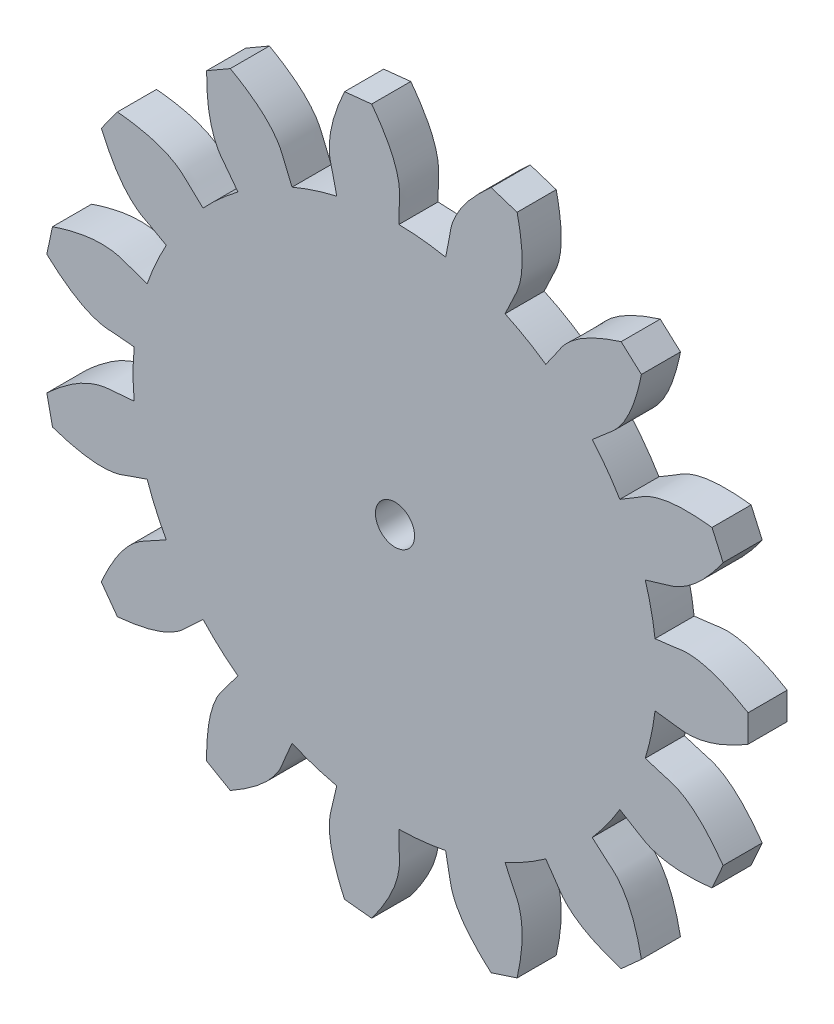
SolidWorks part; units mm, degrees
ref_plane "Front Plane" through (0, 0, 0) normal (0, 0, 1) x (1, 0, 0)
ref_plane "Top Plane" through (0, 0, 0) normal (0, 1, 0) x (1, 0, 0)
ref_plane "Right Plane" through (0, 0, 0) normal (1, 0, 0) x (0, 0, -1)
sketch "Sketch1" plane through (0, 0, 0) normal (0, 0, 1) x (1, 0, 0)
  line L0 (-8.1955, 56.7867) -> (-3.7902, 57.2497)
  line L2 (15.6103, 55.2106) -> (19.823, 53.8418)
  line L3 (36.7169, 44.0881) -> (40.0087, 41.1242)
  line L4 (51.4748, 25.3424) -> (53.2764, 21.2959)
  line L5 (57.3323, 2.2148) -> (57.3323, -2.2148)
  line L6 (53.2764, -21.2959) -> (51.4748, -25.3424)
  line L7 (40.0087, -41.1242) -> (36.7169, -44.0881)
  line L8 (19.823, -53.8418) -> (15.6103, -55.2106)
  line L9 (-3.7902, -57.2497) -> (-8.1955, -56.7867)
  line L10 (-26.7481, -50.7586) -> (-30.5842, -48.5438)
  line L11 (-45.081, -35.4908) -> (-47.6846, -31.9073)
  line L12 (-55.6189, -14.0864) -> (-56.5399, -9.7537)
  line L13 (-56.5399, 9.7537) -> (-55.6189, 14.0864)
  line L14 (-47.6846, 31.9073) -> (-45.081, 35.4908)
  line L15 (-30.5842, 48.5438) -> (-26.7481, 50.7586)
  arc A0 (-9.4604, 41.4593) -> (-16.7156, 39.102) centre (0, 0) ccw
  arc A1 (-25.5055, 34.0271) -> (-31.1746, 28.9226) centre (0, 0) ccw
  arc A2 (-37.1405, 20.7113) -> (-40.2433, 13.7423) centre (0, 0) ccw
  arc A3 (-42.3536, 3.8143) -> (-42.3536, -3.8143) centre (0, 0) ccw
  arc A4 (-40.2433, -13.7423) -> (-37.1405, -20.7113) centre (0, 0) ccw
  arc A5 (8.2205, 41.7229) -> (0.6338, 42.5203) centre (0, 0) ccw
  arc A6 (24.48, 34.7722) -> (17.8735, 38.5864) centre (0, 0) ccw
  arc A7 (36.5067, 21.809) -> (32.0228, 27.9806) centre (0, 0) ccw
  arc A8 (42.2211, 5.0749) -> (40.635, 12.5367) centre (0, 0) ccw
  arc A9 (40.635, -12.5367) -> (42.2211, -5.0749) centre (0, 0) ccw
  arc A10 (32.0228, -27.9806) -> (36.5067, -21.809) centre (0, 0) ccw
  arc A11 (17.8735, -38.5864) -> (24.48, -34.7722) centre (0, 0) ccw
  arc A12 (0.6338, -42.5203) -> (8.2205, -41.7229) centre (0, 0) ccw
  arc A13 (-16.7156, -39.102) -> (-9.4604, -41.4593) centre (0, 0) ccw
  arc A14 (-31.1746, -28.9226) -> (-25.5055, -34.0271) centre (0, 0) ccw
  spline S0 degree 3 poles (0.6338, 42.5203) (0.6362, 43.2787) (0.6708, 44.2001) (0.6715, 45.8052) (0.7748, 46.9365) (0.3722, 51.1441) (-1.8992, 54.7005) (-3.7902, 57.2497) knots 0 0 0 0 0.143931 0.175966 0.304305 0.357154 1 1 1 1
  spline S1 degree 3 poles (-9.4604, 41.4593) (-9.6204, 42.2007) (-9.8459, 43.0948) (-10.1802, 44.6647) (-10.5165, 45.7497) (-10.9975, 49.9491) (-9.5152, 53.9) (-8.1955, 56.7867) knots 0 0 0 0 0.143931 0.175966 0.304305 0.357154 1 1 1 1
  spline S2 degree 3 poles (17.8735, 38.5864) (18.1842, 39.2783) (18.5906, 40.106) (19.2441, 41.5721) (19.7986, 42.5635) (21.1422, 46.5711) (20.5137, 50.7438) (19.823, 53.8418) knots 0 0 0 0 0.143931 0.175966 0.304305 0.357154 1 1 1 1
  spline S3 degree 3 poles (8.2205, 41.7229) (8.3759, 42.4653) (8.5336, 43.3737) (8.8666, 44.9439) (9.0008, 46.0719) (10.2694, 50.1039) (13.2305, 53.1103) (15.6103, 55.2106) knots 0 0 0 0 0.143931 0.175966 0.304305 0.357154 1 1 1 1
  spline S4 degree 3 poles (32.0228, 27.9806) (32.5881, 28.4863) (33.296, 29.0772) (34.4892, 30.1507) (35.399, 30.8309) (38.2565, 33.9455) (39.3796, 38.0131) (40.0087, 41.1242) knots 0 0 0 0 0.143931 0.175966 0.304305 0.357154 1 1 1 1
  spline S5 degree 3 poles (24.48, 34.7722) (24.9239, 35.3872) (25.4375, 36.1529) (26.3804, 37.4519) (26.9618, 38.4278) (29.7607, 41.5952) (33.6886, 43.1373) (36.7169, 44.0881) knots 0 0 0 0 0.143931 0.175966 0.304305 0.357154 1 1 1 1
  spline S6 degree 3 poles (40.635, 12.5367) (41.3571, 12.7688) (42.2441, 13.0206) (43.7709, 13.516) (44.8787, 13.7673) (48.756, 15.4504) (51.4363, 18.7096) (53.2764, 21.2959) knots 0 0 0 0 0.143931 0.175966 0.304305 0.357154 1 1 1 1
  spline S7 degree 3 poles (36.5067, 21.809) (37.1624, 22.1903) (37.943, 22.681) (39.3328, 23.4841) (40.2608, 24.1392) (44.106, 25.8944) (48.3216, 25.7055) (51.4748, 25.3424) knots 0 0 0 0 0.143931 0.175966 0.304305 0.357154 1 1 1 1
  spline S8 degree 3 poles (42.2211, -5.0749) (42.9751, -5.1566) (43.8879, -5.2873) (45.4841, -5.4557) (46.5984, -5.6767) (50.8251, -5.7162) (54.5993, -3.829) (57.3323, -2.2148) knots 0 0 0 0 0.143931 0.175966 0.304305 0.357154 1 1 1 1
  spline S9 degree 3 poles (42.2211, 5.0749) (42.9751, 5.1566) (43.8879, 5.2873) (45.4841, 5.4557) (46.5984, 5.6767) (50.8251, 5.7162) (54.5993, 3.829) (57.3323, 2.2148) knots 0 0 0 0 0.143931 0.175966 0.304305 0.357154 1 1 1 1
  spline S10 degree 3 poles (36.5067, -21.809) (37.1624, -22.1903) (37.943, -22.681) (39.3328, -23.4841) (40.2608, -24.1392) (44.106, -25.8944) (48.3216, -25.7055) (51.4748, -25.3424) knots 0 0 0 0 0.143931 0.175966 0.304305 0.357154 1 1 1 1
  spline S11 degree 3 poles (40.635, -12.5367) (41.3571, -12.7688) (42.2441, -13.0206) (43.7709, -13.516) (44.8787, -13.7673) (48.756, -15.4504) (51.4363, -18.7096) (53.2764, -21.2959) knots 0 0 0 0 0.143931 0.175966 0.304305 0.357154 1 1 1 1
  spline S12 degree 3 poles (24.48, -34.7722) (24.9239, -35.3872) (25.4375, -36.1529) (26.3804, -37.4519) (26.9618, -38.4278) (29.7607, -41.5952) (33.6886, -43.1373) (36.7169, -44.0881) knots 0 0 0 0 0.143931 0.175966 0.304305 0.357154 1 1 1 1
  spline S13 degree 3 poles (32.0228, -27.9806) (32.5881, -28.4863) (33.296, -29.0772) (34.4892, -30.1507) (35.399, -30.8309) (38.2565, -33.9455) (39.3796, -38.0131) (40.0087, -41.1242) knots 0 0 0 0 0.143931 0.175966 0.304305 0.357154 1 1 1 1
  spline S14 degree 3 poles (8.2205, -41.7229) (8.3759, -42.4653) (8.5336, -43.3737) (8.8666, -44.9439) (9.0008, -46.0719) (10.2694, -50.1039) (13.2305, -53.1103) (15.6103, -55.2106) knots 0 0 0 0 0.143931 0.175966 0.304305 0.357154 1 1 1 1
  spline S15 degree 3 poles (17.8735, -38.5864) (18.1842, -39.2783) (18.5906, -40.106) (19.2441, -41.5721) (19.7986, -42.5635) (21.1422, -46.5711) (20.5137, -50.7438) (19.823, -53.8418) knots 0 0 0 0 0.143931 0.175966 0.304305 0.357154 1 1 1 1
  spline S16 degree 3 poles (-9.4604, -41.4593) (-9.6204, -42.2007) (-9.8459, -43.0948) (-10.1802, -44.6647) (-10.5165, -45.7497) (-10.9975, -49.9491) (-9.5152, -53.9) (-8.1955, -56.7867) knots 0 0 0 0 0.143931 0.175966 0.304305 0.357154 1 1 1 1
  spline S17 degree 3 poles (0.6338, -42.5203) (0.6362, -43.2787) (0.6708, -44.2001) (0.6715, -45.8052) (0.7748, -46.9365) (0.3722, -51.1441) (-1.8992, -54.7005) (-3.7902, -57.2497) knots 0 0 0 0 0.143931 0.175966 0.304305 0.357154 1 1 1 1
  spline S18 degree 3 poles (-25.5055, -34.0271) (-25.9533, -34.6393) (-26.5229, -35.3644) (-27.4669, -36.6625) (-28.2154, -37.517) (-30.3629, -41.1577) (-30.6157, -45.3699) (-30.5842, -48.5438) knots 0 0 0 0 0.143931 0.175966 0.304305 0.357154 1 1 1 1
  spline S19 degree 3 poles (-16.7156, -39.102) (-17.0219, -39.7959) (-17.365, -40.6517) (-18.0172, -42.1183) (-18.383, -43.1937) (-20.4622, -46.8739) (-23.9837, -49.1989) (-26.7481, -50.7586) knots 0 0 0 0 0.143931 0.175966 0.304305 0.357154 1 1 1 1
  spline S20 degree 3 poles (-37.1405, -20.7113) (-37.7986, -21.0884) (-38.6138, -21.5191) (-40.0042, -22.3211) (-41.0356, -22.7973) (-44.4782, -25.2497) (-46.4224, -28.995) (-47.6846, -31.9073) knots 0 0 0 0 0.143931 0.175966 0.304305 0.357154 1 1 1 1
  spline S21 degree 3 poles (-31.1746, -28.9226) (-31.7367, -29.4319) (-32.3982, -30.0742) (-33.5906, -31.1487) (-34.3622, -31.9824) (-37.7585, -34.4987) (-41.9211, -35.1904) (-45.081, -35.4908) knots 0 0 0 0 0.143931 0.175966 0.304305 0.357154 1 1 1 1
  spline S22 degree 3 poles (-42.3536, -3.8143) (-43.1081, -3.8911) (-44.0281, -3.953) (-45.6245, -4.1202) (-46.7604, -4.1357) (-50.9029, -4.9759) (-54.2023, -7.6065) (-56.5399, -9.7537) knots 0 0 0 0 0.143931 0.175966 0.304305 0.357154 1 1 1 1
  spline S23 degree 3 poles (-40.2433, -13.7423) (-40.9639, -13.9789) (-41.8295, -14.2966) (-43.3559, -14.7932) (-44.3998, -15.241) (-48.526, -16.1584) (-52.6101, -15.0972) (-55.6189, -14.0864) knots 0 0 0 0 0.143931 0.175966 0.304305 0.357154 1 1 1 1
  spline S24 degree 3 poles (-40.2433, 13.7423) (-40.9639, 13.9789) (-41.8295, 14.2966) (-43.3559, 14.7932) (-44.3998, 15.241) (-48.526, 16.1584) (-52.6101, 15.0972) (-55.6189, 14.0864) knots 0 0 0 0 0.143931 0.175966 0.304305 0.357154 1 1 1 1
  spline S25 degree 3 poles (-42.3536, 3.8143) (-43.1081, 3.8911) (-44.0281, 3.953) (-45.6245, 4.1202) (-46.7604, 4.1357) (-50.9029, 4.9759) (-54.2023, 7.6065) (-56.5399, 9.7537) knots 0 0 0 0 0.143931 0.175966 0.304305 0.357154 1 1 1 1
  spline S26 degree 3 poles (-31.1746, 28.9226) (-31.7367, 29.4319) (-32.3982, 30.0742) (-33.5906, 31.1487) (-34.3622, 31.9824) (-37.7585, 34.4987) (-41.9211, 35.1904) (-45.081, 35.4908) knots 0 0 0 0 0.143931 0.175966 0.304305 0.357154 1 1 1 1
  spline S27 degree 3 poles (-37.1405, 20.7113) (-37.7986, 21.0884) (-38.6138, 21.5191) (-40.0042, 22.3211) (-41.0356, 22.7973) (-44.4782, 25.2497) (-46.4224, 28.995) (-47.6846, 31.9073) knots 0 0 0 0 0.143931 0.175966 0.304305 0.357154 1 1 1 1
  spline S28 degree 3 poles (-16.7156, 39.102) (-17.0219, 39.7959) (-17.365, 40.6517) (-18.0172, 42.1183) (-18.383, 43.1937) (-20.4622, 46.8739) (-23.9837, 49.1989) (-26.7481, 50.7586) knots 0 0 0 0 0.143931 0.175966 0.304305 0.357154 1 1 1 1
  spline S29 degree 3 poles (-25.5055, 34.0271) (-25.9533, 34.6393) (-26.5229, 35.3644) (-27.4669, 36.6625) (-28.2154, 37.517) (-30.3629, 41.1577) (-30.6157, 45.3699) (-30.5842, 48.5438) knots 0 0 0 0 0.143931 0.175966 0.304305 0.357154 1 1 1 1
  point P156 (0, 0)
  dimension "D1" = 15
sketch "Sketch2" plane through (0, 0, 0) normal (0, 0, 1) x (1, 0, 0)
  line L15 (-55.6189, 14.0864) -> (-56.5399, 9.7537)
  line L16 (-56.5399, -9.7537) -> (-55.6189, -14.0864)
  line L17 (-47.6846, -31.9073) -> (-45.081, -35.4908)
  line L18 (-30.5842, -48.5438) -> (-26.7481, -50.7586)
  line L19 (-8.1955, -56.7867) -> (-3.7902, -57.2497)
  line L20 (15.6103, -55.2106) -> (19.823, -53.8418)
  line L21 (36.7169, -44.0881) -> (40.0087, -41.1242)
  line L22 (51.4748, -25.3424) -> (53.2764, -21.2959)
  line L23 (57.3323, -2.2148) -> (57.3323, 2.2148)
  line L24 (53.2764, 21.2959) -> (51.4748, 25.3424)
  line L25 (40.0087, 41.1242) -> (36.7169, 44.0881)
  line L26 (19.823, 53.8418) -> (15.6103, 55.2106)
  line L27 (-3.7902, 57.2497) -> (-8.1955, 56.7867)
  line L28 (-26.7481, 50.7586) -> (-30.5842, 48.5438)
  line L29 (-45.081, 35.4908) -> (-47.6846, 31.9073)
  line L30 (-55.6189, 14.0864) -> (-56.5399, 9.7537)
  line L31 (-56.5399, -9.7537) -> (-55.6189, -14.0864)
  line L32 (-47.6846, -31.9073) -> (-45.081, -35.4908)
  line L33 (-30.5842, -48.5438) -> (-26.7481, -50.7586)
  line L34 (-8.1955, -56.7867) -> (-3.7902, -57.2497)
  line L35 (15.6103, -55.2106) -> (19.823, -53.8418)
  line L36 (36.7169, -44.0881) -> (40.0087, -41.1242)
  line L37 (51.4748, -25.3424) -> (53.2764, -21.2959)
  line L38 (57.3323, -2.2148) -> (57.3323, 2.2148)
  line L39 (53.2764, 21.2959) -> (51.4748, 25.3424)
  line L40 (40.0087, 41.1242) -> (36.7169, 44.0881)
  line L41 (19.823, 53.8418) -> (15.6103, 55.2106)
  line L42 (-3.7902, 57.2497) -> (-8.1955, 56.7867)
  line L43 (-26.7481, 50.7586) -> (-30.5842, 48.5438)
  line L44 (-45.081, 35.4908) -> (-47.6846, 31.9073)
  line L48 (-3.2317, -2.4041) -> (-3.5907, -2.6712) construction
  line L49 (-2.6712, -3.5907) -> (-2.4041, -3.2317) construction
  line L50 (-1.5967, -3.6978) -> (-1.774, -4.1086) construction
  line L51 (-0.5179, -4.4452) -> (-0.4662, -4.0008) construction
  line L52 (0.4662, -4.0008) -> (0.5179, -4.4452) construction
  line L53 (1.774, -4.1086) -> (1.5967, -3.6978) construction
  line L54 (2.4041, -3.2317) -> (2.6712, -3.5907) construction
  line L55 (3.5907, -2.6712) -> (3.2317, -2.4041) construction
  line L56 (3.6978, -1.5967) -> (4.1086, -1.774) construction
  line L57 (4.4452, -0.5179) -> (4.0008, -0.4662) construction
  line L58 (4.0008, 0.4662) -> (4.4452, 0.5179) construction
  line L59 (4.1086, 1.774) -> (3.6978, 1.5967) construction
  line L60 (3.2317, 2.4041) -> (3.5907, 2.6712) construction
  line L61 (2.6712, 3.5907) -> (2.4041, 3.2317) construction
  line L62 (1.5967, 3.6978) -> (1.774, 4.1086) construction
  line L63 (0.5179, 4.4452) -> (0.4662, 4.0008) construction
  line L64 (-0.4662, 4.0008) -> (-0.5179, 4.4452) construction
  line L65 (-1.774, 4.1086) -> (-1.5967, 3.6978) construction
  line L66 (-2.4041, 3.2317) -> (-2.6712, 3.5907) construction
  line L67 (-3.5907, 2.6712) -> (-3.2317, 2.4041) construction
  line L68 (-3.6978, 1.5967) -> (-4.1086, 1.774) construction
  line L69 (-4.4452, 0.5179) -> (-4.0008, 0.4662) construction
  line L70 (-4.0008, -0.4662) -> (-4.4452, -0.5179) construction
  line L71 (-4.1086, -1.774) -> (-3.6978, -1.5967) construction
  arc A15 (-37.1405, 20.7113) -> (-40.2433, 13.7423) centre (0, 0) ccw
  arc A16 (-42.3536, 3.8143) -> (-42.3536, -3.8143) centre (0, 0) ccw
  arc A17 (-40.2433, -13.7423) -> (-37.1405, -20.7113) centre (0, 0) ccw
  arc A18 (-31.1746, -28.9226) -> (-25.5055, -34.0271) centre (0, 0) ccw
  arc A19 (-16.7156, -39.102) -> (-9.4604, -41.4593) centre (0, 0) ccw
  arc A20 (0.6338, -42.5203) -> (8.2205, -41.7229) centre (0, 0) ccw
  arc A21 (17.8735, -38.5864) -> (24.48, -34.7722) centre (0, 0) ccw
  arc A22 (32.0228, -27.9806) -> (36.5067, -21.809) centre (0, 0) ccw
  arc A23 (40.635, -12.5367) -> (42.2211, -5.0749) centre (0, 0) ccw
  arc A24 (42.2211, 5.0749) -> (40.635, 12.5367) centre (0, 0) ccw
  arc A25 (36.5067, 21.809) -> (32.0228, 27.9806) centre (0, 0) ccw
  arc A26 (24.48, 34.7722) -> (17.8735, 38.5864) centre (0, 0) ccw
  arc A27 (8.2205, 41.7229) -> (0.6338, 42.5203) centre (0, 0) ccw
  arc A28 (-9.4604, 41.4593) -> (-16.7156, 39.102) centre (0, 0) ccw
  arc A29 (-25.5055, 34.0271) -> (-31.1746, 28.9226) centre (0, 0) ccw
  arc A30 (-37.1405, 20.7113) -> (-40.2433, 13.7423) centre (0, 0) ccw
  arc A31 (-42.3536, 3.8143) -> (-42.3536, -3.8143) centre (0, 0) ccw
  arc A32 (-40.2433, -13.7423) -> (-37.1405, -20.7113) centre (0, 0) ccw
  arc A33 (-31.1746, -28.9226) -> (-25.5055, -34.0271) centre (0, 0) ccw
  arc A34 (-16.7156, -39.102) -> (-9.4604, -41.4593) centre (0, 0) ccw
  arc A35 (0.6338, -42.5203) -> (8.2205, -41.7229) centre (0, 0) ccw
  arc A36 (17.8735, -38.5864) -> (24.48, -34.7722) centre (0, 0) ccw
  arc A37 (32.0228, -27.9806) -> (36.5067, -21.809) centre (0, 0) ccw
  arc A38 (40.635, -12.5367) -> (42.2211, -5.0749) centre (0, 0) ccw
  arc A39 (42.2211, 5.0749) -> (40.635, 12.5367) centre (0, 0) ccw
  arc A40 (36.5067, 21.809) -> (32.0228, 27.9806) centre (0, 0) ccw
  arc A41 (24.48, 34.7722) -> (17.8735, 38.5864) centre (0, 0) ccw
  arc A42 (8.2205, 41.7229) -> (0.6338, 42.5203) centre (0, 0) ccw
  arc A43 (-9.4604, 41.4593) -> (-16.7156, 39.102) centre (0, 0) ccw
  arc A44 (-25.5055, 34.0271) -> (-31.1746, 28.9226) centre (0, 0) ccw
  circle A78 centre (0, 0) radius 3.175
  arc A96 (-4.0992, -3.7508) -> (-3.7508, -4.0992) centre (0, 0) ccw construction
  arc A97 (-2.0459, -3.1669) -> (-2.4041, -3.2317) centre (-2.1904, -3.3906) ccw construction
  arc A98 (-2.0459, -3.1669) -> (-1.7197, -3.3553) centre (0, 0) ccw construction
  arc A99 (-1.5967, -3.6978) -> (-1.7197, -3.3553) centre (-1.8412, -3.5923) ccw construction
  arc A100 (-1.6746, -5.2979) -> (-1.1987, -5.4254) centre (0, 0) ccw construction
  arc A101 (-0.1883, -3.7656) -> (-0.4662, -4.0008) centre (-0.2016, -4.0316) ccw construction
  arc A102 (-0.1883, -3.7656) -> (0.1883, -3.7656) centre (0, 0) ccw construction
  arc A103 (0.4662, -4.0008) -> (0.1883, -3.7656) centre (0.2016, -4.0316) ccw construction
  arc A104 (1.1987, -5.4254) -> (1.6746, -5.2979) centre (0, 0) ccw construction
  arc A105 (1.7197, -3.3553) -> (1.5967, -3.6978) centre (1.8412, -3.5923) ccw construction
  arc A106 (1.7197, -3.3553) -> (2.0459, -3.1669) centre (0, 0) ccw construction
  arc A107 (2.4041, -3.2317) -> (2.0459, -3.1669) centre (2.1904, -3.3906) ccw construction
  arc A108 (3.7508, -4.0992) -> (4.0992, -3.7508) centre (0, 0) ccw construction
  arc A109 (3.1669, -2.0459) -> (3.2317, -2.4041) centre (3.3906, -2.1904) ccw construction
  arc A110 (3.1669, -2.0459) -> (3.3553, -1.7197) centre (0, 0) ccw construction
  arc A111 (3.6978, -1.5967) -> (3.3553, -1.7197) centre (3.5923, -1.8412) ccw construction
  arc A112 (5.2979, -1.6746) -> (5.4254, -1.1987) centre (0, 0) ccw construction
  arc A113 (3.7656, -0.1883) -> (4.0008, -0.4662) centre (4.0316, -0.2016) ccw construction
  arc A114 (3.7656, -0.1883) -> (3.7656, 0.1883) centre (0, 0) ccw construction
  arc A115 (4.0008, 0.4662) -> (3.7656, 0.1883) centre (4.0316, 0.2016) ccw construction
  arc A116 (5.4254, 1.1987) -> (5.2979, 1.6746) centre (0, 0) ccw construction
  arc A117 (3.3553, 1.7197) -> (3.6978, 1.5967) centre (3.5923, 1.8412) ccw construction
  arc A118 (3.3553, 1.7197) -> (3.1669, 2.0459) centre (0, 0) ccw construction
  arc A119 (3.2317, 2.4041) -> (3.1669, 2.0459) centre (3.3906, 2.1904) ccw construction
  arc A120 (4.0992, 3.7508) -> (3.7508, 4.0992) centre (0, 0) ccw construction
  arc A121 (2.0459, 3.1669) -> (2.4041, 3.2317) centre (2.1904, 3.3906) ccw construction
  arc A122 (2.0459, 3.1669) -> (1.7197, 3.3553) centre (0, 0) ccw construction
  arc A123 (1.5967, 3.6978) -> (1.7197, 3.3553) centre (1.8412, 3.5923) ccw construction
  arc A124 (1.6746, 5.2979) -> (1.1987, 5.4254) centre (0, 0) ccw construction
  arc A125 (0.1883, 3.7656) -> (0.4662, 4.0008) centre (0.2016, 4.0316) ccw construction
  arc A126 (0.1883, 3.7656) -> (-0.1883, 3.7656) centre (0, 0) ccw construction
  arc A127 (-0.4662, 4.0008) -> (-0.1883, 3.7656) centre (-0.2016, 4.0316) ccw construction
  arc A128 (-1.1987, 5.4254) -> (-1.6746, 5.2979) centre (0, 0) ccw construction
  arc A129 (-1.7197, 3.3553) -> (-1.5967, 3.6978) centre (-1.8412, 3.5923) ccw construction
  arc A130 (-1.7197, 3.3553) -> (-2.0459, 3.1669) centre (0, 0) ccw construction
  arc A131 (-2.4041, 3.2317) -> (-2.0459, 3.1669) centre (-2.1904, 3.3906) ccw construction
  arc A132 (-3.7508, 4.0992) -> (-4.0992, 3.7508) centre (0, 0) ccw construction
  arc A133 (-3.1669, 2.0459) -> (-3.2317, 2.4041) centre (-3.3906, 2.1904) ccw construction
  arc A134 (-3.1669, 2.0459) -> (-3.3553, 1.7197) centre (0, 0) ccw construction
  arc A135 (-3.6978, 1.5967) -> (-3.3553, 1.7197) centre (-3.5923, 1.8412) ccw construction
  arc A136 (-5.2979, 1.6746) -> (-5.4254, 1.1987) centre (0, 0) ccw construction
  arc A137 (-3.7656, 0.1883) -> (-4.0008, 0.4662) centre (-4.0316, 0.2016) ccw construction
  arc A138 (-3.7656, 0.1883) -> (-3.7656, -0.1883) centre (0, 0) ccw construction
  arc A139 (-4.0008, -0.4662) -> (-3.7656, -0.1883) centre (-4.0316, -0.2016) ccw construction
  arc A140 (-5.4254, -1.1987) -> (-5.2979, -1.6746) centre (0, 0) ccw construction
  arc A141 (-3.3553, -1.7197) -> (-3.6978, -1.5967) centre (-3.5923, -1.8412) ccw construction
  arc A142 (-3.3553, -1.7197) -> (-3.1669, -2.0459) centre (0, 0) ccw construction
  arc A143 (-3.2317, -2.4041) -> (-3.1669, -2.0459) centre (-3.3906, -2.1904) ccw construction
  spline S30 degree 3 poles (-302.6488, -2956.9254) (18.3301, 290.9407) (-74.9048, 46.9251) (-41.0356, 22.7973) (-40.0042, 22.3211) (-13.2069, 6.8646) (24.9688, 26.8274) (-941.9134, -2838.7443) knots -7.282953 -7.282953 -7.282953 -7.282953 0.642846 0.695695 0.824034 0.856069 6.560618 6.560618 6.560618 6.560618 only from (-47.6846, 31.9073) to (-37.1405, 20.7113)
  spline S31 degree 3 poles (1479.326, 2599.4526) (-3.2293, -36.5063) (-13.9386, 5.2213) (-43.3559, 14.7932) (-44.3998, 15.241) (-84.9936, 24.2662) (-203.9476, -208.3028) (1994.962, 2203.5358) knots -5.560606 -5.560606 -5.560606 -5.560606 0.143931 0.175966 0.304305 0.357154 8.283013 8.283013 8.283013 8.283013 only from (-40.2433, 13.7423) to (-55.6189, 14.0864)
  spline S32 degree 3 poles (926.2064, -2824.3841) (-101.5909, 273.2431) (-87.5151, 12.4017) (-46.7604, 4.1357) (-45.6245, 4.1202) (-14.8572, 0.8994) (11.8984, 34.6638) (294.1406, -2976.4327) knots -7.282953 -7.282953 -7.282953 -7.282953 0.642846 0.695695 0.824034 0.856069 6.560618 6.560618 6.560618 6.560618 only from (-56.5399, 9.7537) to (-42.3536, 3.8143)
  spline S33 degree 3 poles (294.1389, 2976.4142) (11.8983, -34.6636) (-14.8573, -0.8994) (-45.6245, -4.1202) (-46.7604, -4.1357) (-87.5154, -12.4018) (-101.5911, -273.247) (926.2297, 2824.4543) knots -5.560606 -5.560606 -5.560606 -5.560606 0.143931 0.175966 0.304305 0.357154 8.283013 8.283013 8.283013 8.283013 only from (-42.3536, -3.8143) to (-56.5399, -9.7537)
  spline S34 degree 3 poles (1994.9122, -2203.4812) (-203.9459, 208.2993) (-84.9933, -24.2661) (-44.3998, -15.241) (-43.3559, -14.7932) (-13.9385, -5.2213) (-3.2293, 36.5064) (1479.3351, -2599.4688) knots -7.282953 -7.282953 -7.282953 -7.282953 0.642846 0.695695 0.824034 0.856069 6.560618 6.560618 6.560618 6.560618 only from (-55.6189, -14.0864) to (-40.2433, -13.7423)
  spline S35 degree 3 poles (-941.9075, 2838.7268) (24.9686, -26.8273) (-13.207, -6.8646) (-40.0042, -22.3211) (-41.0356, -22.7973) (-74.9051, -46.9253) (18.3315, -290.9444) (-302.6561, 2956.999) knots -5.560606 -5.560606 -5.560606 -5.560606 0.143931 0.175966 0.304305 0.357154 8.283013 8.283013 8.283013 8.283013 only from (-37.1405, -20.7113) to (-47.6846, -31.9073)
  spline S36 degree 3 poles (2718.6795, -1201.5763) (-271.0368, 107.3386) (-67.7753, -56.7381) (-34.3622, -31.9824) (-33.5906, -31.1487) (-10.6098, -10.4392) (-17.7986, 32.0368) (2408.739, -1773.0331) knots -7.282953 -7.282953 -7.282953 -7.282953 0.642846 0.695695 0.824034 0.856069 6.560618 6.560618 6.560618 6.560618 only from (-45.081, -35.4908) to (-31.1746, -28.9226)
  spline S37 degree 3 poles (-2015.0895, 2210.1977) (33.7216, -14.3523) (-9.273, -11.6429) (-27.4669, -36.6625) (-28.2154, -37.517) (-49.343, -73.3351) (135.0844, -258.3348) (-1479.21, 2578.2516) knots -5.560606 -5.560606 -5.560606 -5.560606 0.143931 0.175966 0.304305 0.357154 8.283013 8.283013 8.283013 8.283013 only from (-25.5055, -34.0271) to (-30.5842, -48.5438)
  spline S38 degree 3 poles (2972.3624, 8.092) (-291.2629, -12.1819) (-38.8384, -79.3995) (-18.383, -43.1937) (-18.0172, -42.1183) (-5.4465, -13.8521) (-29.2904, 22.0277) (2921.6502, -640.0239) knots -7.282953 -7.282953 -7.282953 -7.282953 0.642846 0.695695 0.824034 0.856069 6.560618 6.560618 6.560618 6.560618 only from (-26.7481, -50.7586) to (-16.7156, -39.102)
  spline S39 degree 3 poles (-2739.8442, 1199.5053) (36.6438, 0.6043) (-3.7357, -14.408) (-10.1802, -44.6647) (-10.5165, -45.7497) (-15.249, -87.0645) (228.48, -181.0568) (-2399.995, 1753.7012) knots -5.560606 -5.560606 -5.560606 -5.560606 0.143931 0.175966 0.304305 0.357154 8.283013 8.283013 8.283013 8.283013 only from (-9.4604, -41.4593) to (-8.1955, -56.7867)
  spline S40 degree 3 poles (2712.0969, 1216.3611) (-261.1271, -129.596) (-3.1859, -88.3321) (0.7748, -46.9365) (0.6715, -45.8052) (0.6585, -14.8698) (-35.7176, 8.2099) (2929.3814, 603.6512) knots -7.282953 -7.282953 -7.282953 -7.282953 0.642846 0.695695 0.824034 0.856069 6.560618 6.560618 6.560618 6.560618 only from (-3.7902, -57.2497) to (0.6338, -42.5203)
  spline S41 degree 3 poles (-2990.855, -18.5924) (33.23, 15.4565) (2.4475, -14.6819) (8.8666, -44.9439) (9.0008, -46.0719) (21.4817, -85.7397) (282.3693, -72.4725) (-2905.799, 625.9199) knots -5.560606 -5.560606 -5.560606 -5.560606 0.143931 0.175966 0.304305 0.357154 8.283013 8.283013 8.283013 8.283013 only from (8.2205, -41.7229) to (15.6103, -55.2106)
  spline S42 degree 3 poles (1982.8852, 2214.3103) (-185.84, -224.6018) (33.0174, -81.9912) (19.7986, -42.5635) (19.2441, -41.5721) (6.6497, -13.3164) (-35.9689, -7.0276) (2430.596, 1742.9496) knots -7.282953 -7.282953 -7.282953 -7.282953 0.642846 0.695695 0.824034 0.856069 6.560618 6.560618 6.560618 6.560618 only from (19.823, -53.8418) to (17.8735, -38.5864)
  spline S43 degree 3 poles (-2724.7198, -1233.4754) (24.0704, 27.636) (8.2075, -12.4171) (26.3804, -37.4519) (26.9618, -38.4278) (54.498, -69.5897) (287.4344, 48.6431) (-2909.164, -610.0887) knots -5.560606 -5.560606 -5.560606 -5.560606 0.143931 0.175966 0.304305 0.357154 8.283013 8.283013 8.283013 8.283013 only from (24.48, -34.7722) to (36.7169, -44.0881)
  spline S44 degree 3 poles (910.8146, 2829.3852) (-78.4195, -280.7719) (63.5117, -61.4733) (35.399, -30.8309) (34.4892, -30.1507) (11.4911, -9.4605) (-30.0009, -21.0499) (1511.5385, 2580.8761) knots -7.282953 -7.282953 -7.282953 -7.282953 0.642846 0.695695 0.824034 0.856069 6.560618 6.560618 6.560618 6.560618 only from (40.0087, -41.1242) to (32.0228, -27.9806)
  spline S45 degree 3 poles (-1987.4557, -2235.0792) (10.7488, 35.0371) (12.5484, -8.0052) (39.3328, -23.4841) (40.2608, -24.1392) (78.0911, -41.407) (242.7995, 161.3478) (-2409.5082, -1740.6074) knots -5.560606 -5.560606 -5.560606 -5.560606 0.143931 0.175966 0.304305 0.357154 8.283013 8.283013 8.283013 8.283013 only from (36.5067, -21.809) to (51.4748, -25.3424)
  spline S46 degree 3 poles (-318.7441, 2955.2337) (42.5604, -288.394) (83.0243, -30.3261) (44.8787, -13.7673) (43.7709, -13.516) (14.3455, -3.9687) (-18.8454, -31.4324) (331.1222, 2972.5458) knots -7.282953 -7.282953 -7.282953 -7.282953 0.642846 0.695695 0.824034 0.856069 6.560618 6.560618 6.560618 6.560618 only from (53.2764, -21.2959) to (40.635, -12.5367)
  spline S47 degree 3 poles (-906.5426, -2850.2175) (-4.4313, 36.3799) (14.7196, -2.2092) (45.4841, -5.4557) (46.5984, -5.6767) (88.1815, -6.0647) (156.1823, 246.154) (-1493.2264, -2570.1592) knots -5.560606 -5.560606 -5.560606 -5.560606 0.143931 0.175966 0.304305 0.357154 8.283013 8.283013 8.283013 8.283013 only from (42.2211, -5.0749) to (57.3323, -2.2148)
  spline S48 degree 4 poles (-3.5907, -2.6712) (-3.5921, -2.6723) (-3.596, -2.6754) (-3.6078, -2.6855) (-3.6301, -2.7066) (-3.6561, -2.7344) (-3.6845, -2.7679) (-3.7107, -2.8014) (-3.7323, -2.8307) (-3.7532, -2.8607) (-3.7733, -2.8911) (-3.7969, -2.9286) (-3.8241, -2.9744) (-3.8542, -3.0293) (-3.8864, -3.0931) (-3.917, -3.1596) (-3.9454, -3.2263) (-3.972, -3.2951) (-3.9963, -3.3625) (-4.0194, -3.4339) (-4.0396, -3.5005) (-4.0598, -3.5764) (-4.0753, -3.6381) (-4.0894, -3.7029) (-4.096, -3.7345) (-4.0992, -3.7508) knots 0 0 0 0 0 0.005377 0.015084 0.04661 0.092111 0.119476 0.146842 0.174209 0.201575 0.228941 0.256307 0.307035 0.361767 0.4165 0.471232 0.525964 0.580697 0.635429 0.690161 0.744894 0.799626 0.854358 0.909091 0.909091 0.909091 0.909091 0.909091 construction
  spline S49 degree 4 poles (-3.7508, -4.0992) (-3.7345, -4.096) (-3.7029, -4.0894) (-3.6381, -4.0753) (-3.5764, -4.0598) (-3.5005, -4.0396) (-3.4339, -4.0194) (-3.3625, -3.9963) (-3.2951, -3.972) (-3.2263, -3.9454) (-3.1596, -3.917) (-3.0931, -3.8864) (-3.0293, -3.8542) (-2.9744, -3.8241) (-2.9286, -3.7969) (-2.8911, -3.7733) (-2.8607, -3.7532) (-2.8307, -3.7323) (-2.8014, -3.7107) (-2.7679, -3.6845) (-2.7378, -3.659) (-2.7123, -3.6354) (-2.692, -3.6147) (-2.6816, -3.6033) (-2.6754, -3.596) (-2.6723, -3.5921) (-2.6712, -3.5907) knots 0 0 0 0 0 0.054733 0.109465 0.164197 0.21893 0.273662 0.328394 0.383127 0.437859 0.492591 0.547324 0.602056 0.652784 0.68015 0.707516 0.734882 0.762248 0.789615 0.81698 0.862481 0.880559 0.894007 0.903714 0.909091 0.909091 0.909091 0.909091 0.909091 construction
  spline S50 degree 4 poles (-1.774, -4.1086) (-1.7747, -4.1103) (-1.7766, -4.115) (-1.7817, -4.1296) (-1.7905, -4.1591) (-1.7991, -4.1961) (-1.8069, -4.2393) (-1.8129, -4.2814) (-1.8169, -4.3177) (-1.82, -4.354) (-1.8223, -4.3904) (-1.8239, -4.4347) (-1.8245, -4.488) (-1.8231, -4.5506) (-1.8191, -4.6219) (-1.8124, -4.6948) (-1.8037, -4.7668) (-1.7923, -4.8396) (-1.7796, -4.9102) (-1.7639, -4.9835) (-1.7481, -5.0513) (-1.7277, -5.1271) (-1.7103, -5.1883) (-1.6901, -5.2515) (-1.6799, -5.2822) (-1.6746, -5.2979) knots 0 0 0 0 0 0.005377 0.015084 0.04661 0.092111 0.119476 0.146842 0.174209 0.201575 0.228941 0.256307 0.307035 0.361767 0.4165 0.471232 0.525964 0.580697 0.635429 0.690161 0.744894 0.799626 0.854358 0.909091 0.909091 0.909091 0.909091 0.909091 construction
  spline S51 degree 4 poles (-1.1987, -5.4254) (-1.1862, -5.4145) (-1.1621, -5.393) (-1.113, -5.3484) (-1.0674, -5.304) (-1.0117, -5.2486) (-0.9642, -5.1978) (-0.9139, -5.1422) (-0.8676, -5.0874) (-0.8214, -5.03) (-0.7778, -4.9721) (-0.7355, -4.9122) (-0.6964, -4.8525) (-0.6639, -4.799) (-0.6378, -4.7525) (-0.6171, -4.7133) (-0.6008, -4.6807) (-0.5853, -4.6477) (-0.5707, -4.6143) (-0.5548, -4.5748) (-0.5415, -4.5377) (-0.5312, -4.5045) (-0.524, -4.4765) (-0.5207, -4.4613) (-0.5189, -4.452) (-0.5182, -4.447) (-0.5179, -4.4452) knots 0 0 0 0 0 0.054733 0.109465 0.164197 0.21893 0.273662 0.328394 0.383127 0.437859 0.492591 0.547324 0.602056 0.652784 0.68015 0.707516 0.734882 0.762248 0.789615 0.81698 0.862481 0.880559 0.894007 0.903714 0.909091 0.909091 0.909091 0.909091 0.909091 construction
  spline S52 degree 4 poles (0.5179, -4.4452) (0.5182, -4.447) (0.5189, -4.452) (0.5218, -4.4672) (0.529, -4.4971) (0.54, -4.5335) (0.5548, -4.5748) (0.5707, -4.6143) (0.5853, -4.6477) (0.6008, -4.6807) (0.6171, -4.7133) (0.6378, -4.7525) (0.6639, -4.799) (0.6964, -4.8525) (0.7355, -4.9122) (0.7778, -4.9721) (0.8214, -5.03) (0.8676, -5.0874) (0.9139, -5.1422) (0.9642, -5.1978) (1.0117, -5.2486) (1.0674, -5.304) (1.113, -5.3484) (1.1621, -5.393) (1.1862, -5.4145) (1.1987, -5.4254) knots 0 0 0 0 0 0.005377 0.015084 0.04661 0.092111 0.119476 0.146842 0.174209 0.201575 0.228941 0.256307 0.307035 0.361767 0.4165 0.471232 0.525964 0.580697 0.635429 0.690161 0.744894 0.799626 0.854358 0.909091 0.909091 0.909091 0.909091 0.909091 construction
  spline S53 degree 4 poles (1.6746, -5.2979) (1.6799, -5.2822) (1.6901, -5.2515) (1.7103, -5.1883) (1.7277, -5.1271) (1.7481, -5.0513) (1.7639, -4.9835) (1.7796, -4.9102) (1.7923, -4.8396) (1.8037, -4.7668) (1.8124, -4.6948) (1.8191, -4.6219) (1.8231, -4.5506) (1.8245, -4.488) (1.8239, -4.4347) (1.8223, -4.3904) (1.82, -4.354) (1.8169, -4.3177) (1.8129, -4.2814) (1.8069, -4.2393) (1.7999, -4.2005) (1.7922, -4.1666) (1.7844, -4.1387) (1.7797, -4.1239) (1.7766, -4.115) (1.7747, -4.1103) (1.774, -4.1086) knots 0 0 0 0 0 0.054733 0.109465 0.164197 0.21893 0.273662 0.328394 0.383127 0.437859 0.492591 0.547324 0.602056 0.652784 0.68015 0.707516 0.734882 0.762248 0.789615 0.81698 0.862481 0.880559 0.894007 0.903714 0.909091 0.909091 0.909091 0.909091 0.909091 construction
  spline S54 degree 4 poles (2.6712, -3.5907) (2.6723, -3.5921) (2.6754, -3.596) (2.6855, -3.6078) (2.7066, -3.6301) (2.7344, -3.6561) (2.7679, -3.6845) (2.8014, -3.7107) (2.8307, -3.7323) (2.8607, -3.7532) (2.8911, -3.7733) (2.9286, -3.7969) (2.9744, -3.8241) (3.0293, -3.8542) (3.0931, -3.8864) (3.1596, -3.917) (3.2263, -3.9454) (3.2951, -3.972) (3.3625, -3.9963) (3.4339, -4.0194) (3.5005, -4.0396) (3.5764, -4.0598) (3.6381, -4.0753) (3.7029, -4.0894) (3.7345, -4.096) (3.7508, -4.0992) knots 0 0 0 0 0 0.005377 0.015084 0.04661 0.092111 0.119476 0.146842 0.174209 0.201575 0.228941 0.256307 0.307035 0.361767 0.4165 0.471232 0.525964 0.580697 0.635429 0.690161 0.744894 0.799626 0.854358 0.909091 0.909091 0.909091 0.909091 0.909091 construction
  spline S55 degree 4 poles (4.0992, -3.7508) (4.096, -3.7345) (4.0894, -3.7029) (4.0753, -3.6381) (4.0598, -3.5764) (4.0396, -3.5005) (4.0194, -3.4339) (3.9963, -3.3625) (3.972, -3.2951) (3.9454, -3.2263) (3.917, -3.1596) (3.8864, -3.0931) (3.8542, -3.0293) (3.8241, -2.9744) (3.7969, -2.9286) (3.7733, -2.8911) (3.7532, -2.8607) (3.7323, -2.8307) (3.7107, -2.8014) (3.6845, -2.7679) (3.659, -2.7378) (3.6354, -2.7123) (3.6147, -2.692) (3.6033, -2.6816) (3.596, -2.6754) (3.5921, -2.6723) (3.5907, -2.6712) knots 0 0 0 0 0 0.054733 0.109465 0.164197 0.21893 0.273662 0.328394 0.383127 0.437859 0.492591 0.547324 0.602056 0.652784 0.68015 0.707516 0.734882 0.762248 0.789615 0.81698 0.862481 0.880559 0.894007 0.903714 0.909091 0.909091 0.909091 0.909091 0.909091 construction
  spline S56 degree 4 poles (4.1086, -1.774) (4.1103, -1.7747) (4.115, -1.7766) (4.1296, -1.7817) (4.1591, -1.7905) (4.1961, -1.7991) (4.2393, -1.8069) (4.2814, -1.8129) (4.3177, -1.8169) (4.354, -1.82) (4.3904, -1.8223) (4.4347, -1.8239) (4.488, -1.8245) (4.5506, -1.8231) (4.6219, -1.8191) (4.6948, -1.8124) (4.7668, -1.8037) (4.8396, -1.7923) (4.9102, -1.7796) (4.9835, -1.7639) (5.0513, -1.7481) (5.1271, -1.7277) (5.1883, -1.7103) (5.2515, -1.6901) (5.2822, -1.6799) (5.2979, -1.6746) knots 0 0 0 0 0 0.005377 0.015084 0.04661 0.092111 0.119476 0.146842 0.174209 0.201575 0.228941 0.256307 0.307035 0.361767 0.4165 0.471232 0.525964 0.580697 0.635429 0.690161 0.744894 0.799626 0.854358 0.909091 0.909091 0.909091 0.909091 0.909091 construction
  spline S57 degree 4 poles (5.4254, -1.1987) (5.4145, -1.1862) (5.393, -1.1621) (5.3484, -1.113) (5.304, -1.0674) (5.2486, -1.0117) (5.1978, -0.9642) (5.1422, -0.9139) (5.0874, -0.8676) (5.03, -0.8214) (4.9721, -0.7778) (4.9122, -0.7355) (4.8525, -0.6964) (4.799, -0.6639) (4.7525, -0.6378) (4.7133, -0.6171) (4.6807, -0.6008) (4.6477, -0.5853) (4.6143, -0.5707) (4.5748, -0.5548) (4.5377, -0.5415) (4.5045, -0.5312) (4.4765, -0.524) (4.4613, -0.5207) (4.452, -0.5189) (4.447, -0.5182) (4.4452, -0.5179) knots 0 0 0 0 0 0.054733 0.109465 0.164197 0.21893 0.273662 0.328394 0.383127 0.437859 0.492591 0.547324 0.602056 0.652784 0.68015 0.707516 0.734882 0.762248 0.789615 0.81698 0.862481 0.880559 0.894007 0.903714 0.909091 0.909091 0.909091 0.909091 0.909091 construction
  spline S58 degree 4 poles (4.4452, 0.5179) (4.447, 0.5182) (4.452, 0.5189) (4.4672, 0.5218) (4.4971, 0.529) (4.5335, 0.54) (4.5748, 0.5548) (4.6143, 0.5707) (4.6477, 0.5853) (4.6807, 0.6008) (4.7133, 0.6171) (4.7525, 0.6378) (4.799, 0.6639) (4.8525, 0.6964) (4.9122, 0.7355) (4.9721, 0.7778) (5.03, 0.8214) (5.0874, 0.8676) (5.1422, 0.9139) (5.1978, 0.9642) (5.2486, 1.0117) (5.304, 1.0674) (5.3484, 1.113) (5.393, 1.1621) (5.4145, 1.1862) (5.4254, 1.1987) knots 0 0 0 0 0 0.005377 0.015084 0.04661 0.092111 0.119476 0.146842 0.174209 0.201575 0.228941 0.256307 0.307035 0.361767 0.4165 0.471232 0.525964 0.580697 0.635429 0.690161 0.744894 0.799626 0.854358 0.909091 0.909091 0.909091 0.909091 0.909091 construction
  spline S59 degree 4 poles (5.2979, 1.6746) (5.2822, 1.6799) (5.2515, 1.6901) (5.1883, 1.7103) (5.1271, 1.7277) (5.0513, 1.7481) (4.9835, 1.7639) (4.9102, 1.7796) (4.8396, 1.7923) (4.7668, 1.8037) (4.6948, 1.8124) (4.6219, 1.8191) (4.5506, 1.8231) (4.488, 1.8245) (4.4347, 1.8239) (4.3904, 1.8223) (4.354, 1.82) (4.3177, 1.8169) (4.2814, 1.8129) (4.2393, 1.8069) (4.2005, 1.7999) (4.1666, 1.7922) (4.1387, 1.7844) (4.1239, 1.7797) (4.115, 1.7766) (4.1103, 1.7747) (4.1086, 1.774) knots 0 0 0 0 0 0.054733 0.109465 0.164197 0.21893 0.273662 0.328394 0.383127 0.437859 0.492591 0.547324 0.602056 0.652784 0.68015 0.707516 0.734882 0.762248 0.789615 0.81698 0.862481 0.880559 0.894007 0.903714 0.909091 0.909091 0.909091 0.909091 0.909091 construction
  spline S60 degree 4 poles (3.5907, 2.6712) (3.5921, 2.6723) (3.596, 2.6754) (3.6078, 2.6855) (3.6301, 2.7066) (3.6561, 2.7344) (3.6845, 2.7679) (3.7107, 2.8014) (3.7323, 2.8307) (3.7532, 2.8607) (3.7733, 2.8911) (3.7969, 2.9286) (3.8241, 2.9744) (3.8542, 3.0293) (3.8864, 3.0931) (3.917, 3.1596) (3.9454, 3.2263) (3.972, 3.2951) (3.9963, 3.3625) (4.0194, 3.4339) (4.0396, 3.5005) (4.0598, 3.5764) (4.0753, 3.6381) (4.0894, 3.7029) (4.096, 3.7345) (4.0992, 3.7508) knots 0 0 0 0 0 0.005377 0.015084 0.04661 0.092111 0.119476 0.146842 0.174209 0.201575 0.228941 0.256307 0.307035 0.361767 0.4165 0.471232 0.525964 0.580697 0.635429 0.690161 0.744894 0.799626 0.854358 0.909091 0.909091 0.909091 0.909091 0.909091 construction
  spline S61 degree 4 poles (3.7508, 4.0992) (3.7345, 4.096) (3.7029, 4.0894) (3.6381, 4.0753) (3.5764, 4.0598) (3.5005, 4.0396) (3.4339, 4.0194) (3.3625, 3.9963) (3.2951, 3.972) (3.2263, 3.9454) (3.1596, 3.917) (3.0931, 3.8864) (3.0293, 3.8542) (2.9744, 3.8241) (2.9286, 3.7969) (2.8911, 3.7733) (2.8607, 3.7532) (2.8307, 3.7323) (2.8014, 3.7107) (2.7679, 3.6845) (2.7378, 3.659) (2.7123, 3.6354) (2.692, 3.6147) (2.6816, 3.6033) (2.6754, 3.596) (2.6723, 3.5921) (2.6712, 3.5907) knots 0 0 0 0 0 0.054733 0.109465 0.164197 0.21893 0.273662 0.328394 0.383127 0.437859 0.492591 0.547324 0.602056 0.652784 0.68015 0.707516 0.734882 0.762248 0.789615 0.81698 0.862481 0.880559 0.894007 0.903714 0.909091 0.909091 0.909091 0.909091 0.909091 construction
  spline S62 degree 4 poles (1.774, 4.1086) (1.7747, 4.1103) (1.7766, 4.115) (1.7817, 4.1296) (1.7905, 4.1591) (1.7991, 4.1961) (1.8069, 4.2393) (1.8129, 4.2814) (1.8169, 4.3177) (1.82, 4.354) (1.8223, 4.3904) (1.8239, 4.4347) (1.8245, 4.488) (1.8231, 4.5506) (1.8191, 4.6219) (1.8124, 4.6948) (1.8037, 4.7668) (1.7923, 4.8396) (1.7796, 4.9102) (1.7639, 4.9835) (1.7481, 5.0513) (1.7277, 5.1271) (1.7103, 5.1883) (1.6901, 5.2515) (1.6799, 5.2822) (1.6746, 5.2979) knots 0 0 0 0 0 0.005377 0.015084 0.04661 0.092111 0.119476 0.146842 0.174209 0.201575 0.228941 0.256307 0.307035 0.361767 0.4165 0.471232 0.525964 0.580697 0.635429 0.690161 0.744894 0.799626 0.854358 0.909091 0.909091 0.909091 0.909091 0.909091 construction
  spline S63 degree 4 poles (1.1987, 5.4254) (1.1862, 5.4145) (1.1621, 5.393) (1.113, 5.3484) (1.0674, 5.304) (1.0117, 5.2486) (0.9642, 5.1978) (0.9139, 5.1422) (0.8676, 5.0874) (0.8214, 5.03) (0.7778, 4.9721) (0.7355, 4.9122) (0.6964, 4.8525) (0.6639, 4.799) (0.6378, 4.7525) (0.6171, 4.7133) (0.6008, 4.6807) (0.5853, 4.6477) (0.5707, 4.6143) (0.5548, 4.5748) (0.5415, 4.5377) (0.5312, 4.5045) (0.524, 4.4765) (0.5207, 4.4613) (0.5189, 4.452) (0.5182, 4.447) (0.5179, 4.4452) knots 0 0 0 0 0 0.054733 0.109465 0.164197 0.21893 0.273662 0.328394 0.383127 0.437859 0.492591 0.547324 0.602056 0.652784 0.68015 0.707516 0.734882 0.762248 0.789615 0.81698 0.862481 0.880559 0.894007 0.903714 0.909091 0.909091 0.909091 0.909091 0.909091 construction
  spline S64 degree 4 poles (-0.5179, 4.4452) (-0.5182, 4.447) (-0.5189, 4.452) (-0.5218, 4.4672) (-0.529, 4.4971) (-0.54, 4.5335) (-0.5548, 4.5748) (-0.5707, 4.6143) (-0.5853, 4.6477) (-0.6008, 4.6807) (-0.6171, 4.7133) (-0.6378, 4.7525) (-0.6639, 4.799) (-0.6964, 4.8525) (-0.7355, 4.9122) (-0.7778, 4.9721) (-0.8214, 5.03) (-0.8676, 5.0874) (-0.9139, 5.1422) (-0.9642, 5.1978) (-1.0117, 5.2486) (-1.0674, 5.304) (-1.113, 5.3484) (-1.1621, 5.393) (-1.1862, 5.4145) (-1.1987, 5.4254) knots 0 0 0 0 0 0.005377 0.015084 0.04661 0.092111 0.119476 0.146842 0.174209 0.201575 0.228941 0.256307 0.307035 0.361767 0.4165 0.471232 0.525964 0.580697 0.635429 0.690161 0.744894 0.799626 0.854358 0.909091 0.909091 0.909091 0.909091 0.909091 construction
  spline S65 degree 4 poles (-1.6746, 5.2979) (-1.6799, 5.2822) (-1.6901, 5.2515) (-1.7103, 5.1883) (-1.7277, 5.1271) (-1.7481, 5.0513) (-1.7639, 4.9835) (-1.7796, 4.9102) (-1.7923, 4.8396) (-1.8037, 4.7668) (-1.8124, 4.6948) (-1.8191, 4.6219) (-1.8231, 4.5506) (-1.8245, 4.488) (-1.8239, 4.4347) (-1.8223, 4.3904) (-1.82, 4.354) (-1.8169, 4.3177) (-1.8129, 4.2814) (-1.8069, 4.2393) (-1.7999, 4.2005) (-1.7922, 4.1666) (-1.7844, 4.1387) (-1.7797, 4.1239) (-1.7766, 4.115) (-1.7747, 4.1103) (-1.774, 4.1086) knots 0 0 0 0 0 0.054733 0.109465 0.164197 0.21893 0.273662 0.328394 0.383127 0.437859 0.492591 0.547324 0.602056 0.652784 0.68015 0.707516 0.734882 0.762248 0.789615 0.81698 0.862481 0.880559 0.894007 0.903714 0.909091 0.909091 0.909091 0.909091 0.909091 construction
  spline S66 degree 4 poles (-2.6712, 3.5907) (-2.6723, 3.5921) (-2.6754, 3.596) (-2.6855, 3.6078) (-2.7066, 3.6301) (-2.7344, 3.6561) (-2.7679, 3.6845) (-2.8014, 3.7107) (-2.8307, 3.7323) (-2.8607, 3.7532) (-2.8911, 3.7733) (-2.9286, 3.7969) (-2.9744, 3.8241) (-3.0293, 3.8542) (-3.0931, 3.8864) (-3.1596, 3.917) (-3.2263, 3.9454) (-3.2951, 3.972) (-3.3625, 3.9963) (-3.4339, 4.0194) (-3.5005, 4.0396) (-3.5764, 4.0598) (-3.6381, 4.0753) (-3.7029, 4.0894) (-3.7345, 4.096) (-3.7508, 4.0992) knots 0 0 0 0 0 0.005377 0.015084 0.04661 0.092111 0.119476 0.146842 0.174209 0.201575 0.228941 0.256307 0.307035 0.361767 0.4165 0.471232 0.525964 0.580697 0.635429 0.690161 0.744894 0.799626 0.854358 0.909091 0.909091 0.909091 0.909091 0.909091 construction
  spline S67 degree 4 poles (-4.0992, 3.7508) (-4.096, 3.7345) (-4.0894, 3.7029) (-4.0753, 3.6381) (-4.0598, 3.5764) (-4.0396, 3.5005) (-4.0194, 3.4339) (-3.9963, 3.3625) (-3.972, 3.2951) (-3.9454, 3.2263) (-3.917, 3.1596) (-3.8864, 3.0931) (-3.8542, 3.0293) (-3.8241, 2.9744) (-3.7969, 2.9286) (-3.7733, 2.8911) (-3.7532, 2.8607) (-3.7323, 2.8307) (-3.7107, 2.8014) (-3.6845, 2.7679) (-3.659, 2.7378) (-3.6354, 2.7123) (-3.6147, 2.692) (-3.6033, 2.6816) (-3.596, 2.6754) (-3.5921, 2.6723) (-3.5907, 2.6712) knots 0 0 0 0 0 0.054733 0.109465 0.164197 0.21893 0.273662 0.328394 0.383127 0.437859 0.492591 0.547324 0.602056 0.652784 0.68015 0.707516 0.734882 0.762248 0.789615 0.81698 0.862481 0.880559 0.894007 0.903714 0.909091 0.909091 0.909091 0.909091 0.909091 construction
  spline S68 degree 4 poles (-4.1086, 1.774) (-4.1103, 1.7747) (-4.115, 1.7766) (-4.1296, 1.7817) (-4.1591, 1.7905) (-4.1961, 1.7991) (-4.2393, 1.8069) (-4.2814, 1.8129) (-4.3177, 1.8169) (-4.354, 1.82) (-4.3904, 1.8223) (-4.4347, 1.8239) (-4.488, 1.8245) (-4.5506, 1.8231) (-4.6219, 1.8191) (-4.6948, 1.8124) (-4.7668, 1.8037) (-4.8396, 1.7923) (-4.9102, 1.7796) (-4.9835, 1.7639) (-5.0513, 1.7481) (-5.1271, 1.7277) (-5.1883, 1.7103) (-5.2515, 1.6901) (-5.2822, 1.6799) (-5.2979, 1.6746) knots 0 0 0 0 0 0.005377 0.015084 0.04661 0.092111 0.119476 0.146842 0.174209 0.201575 0.228941 0.256307 0.307035 0.361767 0.4165 0.471232 0.525964 0.580697 0.635429 0.690161 0.744894 0.799626 0.854358 0.909091 0.909091 0.909091 0.909091 0.909091 construction
  spline S69 degree 4 poles (-5.4254, 1.1987) (-5.4145, 1.1862) (-5.393, 1.1621) (-5.3484, 1.113) (-5.304, 1.0674) (-5.2486, 1.0117) (-5.1978, 0.9642) (-5.1422, 0.9139) (-5.0874, 0.8676) (-5.03, 0.8214) (-4.9721, 0.7778) (-4.9122, 0.7355) (-4.8525, 0.6964) (-4.799, 0.6639) (-4.7525, 0.6378) (-4.7133, 0.6171) (-4.6807, 0.6008) (-4.6477, 0.5853) (-4.6143, 0.5707) (-4.5748, 0.5548) (-4.5377, 0.5415) (-4.5045, 0.5312) (-4.4765, 0.524) (-4.4613, 0.5207) (-4.452, 0.5189) (-4.447, 0.5182) (-4.4452, 0.5179) knots 0 0 0 0 0 0.054733 0.109465 0.164197 0.21893 0.273662 0.328394 0.383127 0.437859 0.492591 0.547324 0.602056 0.652784 0.68015 0.707516 0.734882 0.762248 0.789615 0.81698 0.862481 0.880559 0.894007 0.903714 0.909091 0.909091 0.909091 0.909091 0.909091 construction
  spline S70 degree 4 poles (-4.4452, -0.5179) (-4.447, -0.5182) (-4.452, -0.5189) (-4.4672, -0.5218) (-4.4971, -0.529) (-4.5335, -0.54) (-4.5748, -0.5548) (-4.6143, -0.5707) (-4.6477, -0.5853) (-4.6807, -0.6008) (-4.7133, -0.6171) (-4.7525, -0.6378) (-4.799, -0.6639) (-4.8525, -0.6964) (-4.9122, -0.7355) (-4.9721, -0.7778) (-5.03, -0.8214) (-5.0874, -0.8676) (-5.1422, -0.9139) (-5.1978, -0.9642) (-5.2486, -1.0117) (-5.304, -1.0674) (-5.3484, -1.113) (-5.393, -1.1621) (-5.4145, -1.1862) (-5.4254, -1.1987) knots 0 0 0 0 0 0.005377 0.015084 0.04661 0.092111 0.119476 0.146842 0.174209 0.201575 0.228941 0.256307 0.307035 0.361767 0.4165 0.471232 0.525964 0.580697 0.635429 0.690161 0.744894 0.799626 0.854358 0.909091 0.909091 0.909091 0.909091 0.909091 construction
  spline S71 degree 4 poles (-5.2979, -1.6746) (-5.2822, -1.6799) (-5.2515, -1.6901) (-5.1883, -1.7103) (-5.1271, -1.7277) (-5.0513, -1.7481) (-4.9835, -1.7639) (-4.9102, -1.7796) (-4.8396, -1.7923) (-4.7668, -1.8037) (-4.6948, -1.8124) (-4.6219, -1.8191) (-4.5506, -1.8231) (-4.488, -1.8245) (-4.4347, -1.8239) (-4.3904, -1.8223) (-4.354, -1.82) (-4.3177, -1.8169) (-4.2814, -1.8129) (-4.2393, -1.8069) (-4.2005, -1.7999) (-4.1666, -1.7922) (-4.1387, -1.7844) (-4.1239, -1.7797) (-4.115, -1.7766) (-4.1103, -1.7747) (-4.1086, -1.774) knots 0 0 0 0 0 0.054733 0.109465 0.164197 0.21893 0.273662 0.328394 0.383127 0.437859 0.492591 0.547324 0.602056 0.652784 0.68015 0.707516 0.734882 0.762248 0.789615 0.81698 0.862481 0.880559 0.894007 0.903714 0.909091 0.909091 0.909091 0.909091 0.909091 construction
  spline S72 degree 3 poles (-1493.1891, 2570.0954) (156.1813, -246.1502) (88.1812, 6.0647) (46.5984, 5.6767) (45.4841, 5.4557) (14.7195, 2.2092) (-4.4314, -36.3801) (-906.5481, 2850.2352) knots -7.282953 -7.282953 -7.282953 -7.282953 0.642846 0.695695 0.824034 0.856069 6.560618 6.560618 6.560618 6.560618 only from (57.3323, 2.2148) to (42.2211, 5.0749)
  spline S73 degree 3 poles (331.1201, -2972.5273) (-18.8453, 31.4323) (14.3456, 3.9688) (43.7709, 13.516) (44.8787, 13.7673) (83.0245, 30.3262) (42.5598, 288.3979) (-318.7523, -2955.3072) knots -5.560606 -5.560606 -5.560606 -5.560606 0.143931 0.175966 0.304305 0.357154 8.283013 8.283013 8.283013 8.283013 only from (40.635, 12.5367) to (53.2764, 21.2959)
  spline S74 degree 3 poles (-2409.4481, 1740.5643) (242.797, -161.3447) (78.0908, 41.4069) (40.2608, 24.1392) (39.3328, 23.4841) (12.5484, 8.0052) (10.7488, -35.0373) (-1987.468, 2235.0931) knots -7.282953 -7.282953 -7.282953 -7.282953 0.642846 0.695695 0.824034 0.856069 6.560618 6.560618 6.560618 6.560618 only from (51.4748, 25.3424) to (36.5067, 21.809)
  spline S75 degree 3 poles (1511.529, -2580.8602) (-30.0007, 21.0498) (11.4911, 9.4605) (34.4892, 30.1507) (35.399, 30.8309) (63.5119, 61.4735) (-78.4217, 280.7752) (910.837, -2829.4557) knots -5.560606 -5.560606 -5.560606 -5.560606 0.143931 0.175966 0.304305 0.357154 8.283013 8.283013 8.283013 8.283013 only from (32.0228, 27.9806) to (40.0087, 41.1242)
  spline S76 degree 3 poles (-2909.0916, 610.0738) (287.4309, -48.6413) (54.4978, 69.5895) (26.9618, 38.4278) (26.3804, 37.4519) (8.2075, 12.417) (24.0705, -27.6362) (-2724.7366, 1233.4831) knots -7.282953 -7.282953 -7.282953 -7.282953 0.642846 0.695695 0.824034 0.856069 6.560618 6.560618 6.560618 6.560618 only from (36.7169, 44.0881) to (24.48, 34.7722)
  spline S77 degree 3 poles (2430.5809, -1742.9389) (-35.9687, 7.0276) (6.6497, 13.3165) (19.2441, 41.5721) (19.7986, 42.5635) (33.0175, 81.9915) (-185.8433, 224.604) (1982.9343, -2214.3656) knots -5.560606 -5.560606 -5.560606 -5.560606 0.143931 0.175966 0.304305 0.357154 8.283013 8.283013 8.283013 8.283013 only from (17.8735, 38.5864) to (19.823, 53.8418)
  spline S78 degree 3 poles (-2905.7268, -625.904) (282.3654, 72.4727) (21.4816, 85.7394) (9.0008, 46.0719) (8.8666, 44.9439) (2.4475, 14.6818) (33.2301, -15.4566) (-2990.8735, 18.5926) knots -7.282953 -7.282953 -7.282953 -7.282953 0.642846 0.695695 0.824034 0.856069 6.560618 6.560618 6.560618 6.560618 only from (15.6103, 55.2106) to (8.2205, 41.7229)
  spline S79 degree 3 poles (2929.3632, -603.6476) (-35.7174, -8.2098) (0.6585, 14.8699) (0.6715, 45.8052) (0.7748, 46.9365) (-3.186, 88.3324) (-261.131, 129.5966) (2712.1643, -1216.3916) knots -5.560606 -5.560606 -5.560606 -5.560606 0.143931 0.175966 0.304305 0.357154 8.283013 8.283013 8.283013 8.283013 only from (0.6338, 42.5203) to (-3.7902, 57.2497)
  spline S80 degree 3 poles (-2399.9354, -1753.6573) (228.4763, 181.0554) (-15.2489, 87.0642) (-10.5165, 45.7497) (-10.1802, 44.6647) (-3.7357, 14.408) (36.644, -0.6044) (-2739.8612, -1199.5126) knots -7.282953 -7.282953 -7.282953 -7.282953 0.642846 0.695695 0.824034 0.856069 6.560618 6.560618 6.560618 6.560618 only from (-8.1955, 56.7867) to (-9.4604, 41.4593)
  spline S81 degree 3 poles (2921.6321, 640.0199) (-29.2903, -22.0276) (-5.4465, 13.8522) (-18.0172, 42.1183) (-18.383, 43.1937) (-38.8385, 79.3998) (-291.2667, 12.1809) (2972.4364, -8.0924) knots -5.560606 -5.560606 -5.560606 -5.560606 0.143931 0.175966 0.304305 0.357154 8.283013 8.283013 8.283013 8.283013 only from (-16.7156, 39.102) to (-26.7481, 50.7586)
  spline S82 degree 3 poles (-1479.1734, -2578.1874) (135.0816, 258.3321) (-49.3428, 73.3348) (-28.2154, 37.517) (-27.4669, 36.6625) (-9.273, 11.6429) (33.7218, 14.3523) (-2015.1021, -2210.2113) knots -7.282953 -7.282953 -7.282953 -7.282953 0.642846 0.695695 0.824034 0.856069 6.560618 6.560618 6.560618 6.560618 only from (-30.5842, 48.5438) to (-25.5055, 34.0271)
  spline S83 degree 3 poles (2408.7242, 1773.0221) (-17.7986, -32.0366) (-10.6098, 10.4393) (-33.5906, 31.1487) (-34.3622, 31.9824) (-67.7756, 56.7382) (-271.0398, -107.3411) (2718.7473, 1201.606) knots -5.560606 -5.560606 -5.560606 -5.560606 0.143931 0.175966 0.304305 0.357154 8.283013 8.283013 8.283013 8.283013 only from (-31.1746, 28.9226) to (-45.081, 35.4908)
  spline S84 degree 3 poles (-47.6846, 31.9073) (-46.4224, 28.995) (-44.4782, 25.2497) (-41.0356, 22.7973) (-40.0042, 22.3211) (-38.6138, 21.5191) (-37.7986, 21.0884) (-37.1405, 20.7113) knots 0 0 0 0 0.642846 0.695695 0.824034 0.856069 1 1 1 1
  spline S85 degree 3 poles (-40.2433, 13.7423) (-40.9639, 13.9789) (-41.8295, 14.2966) (-43.3559, 14.7932) (-44.3998, 15.241) (-48.526, 16.1584) (-52.6101, 15.0972) (-55.6189, 14.0864) knots 0 0 0 0 0.143931 0.175966 0.304305 0.357154 1 1 1 1
  spline S86 degree 3 poles (-56.5399, 9.7537) (-54.2023, 7.6065) (-50.9029, 4.9759) (-46.7604, 4.1357) (-45.6245, 4.1202) (-44.0281, 3.953) (-43.1081, 3.8911) (-42.3536, 3.8143) knots 0 0 0 0 0.642846 0.695695 0.824034 0.856069 1 1 1 1
  spline S87 degree 3 poles (-42.3536, -3.8143) (-43.1081, -3.8911) (-44.0281, -3.953) (-45.6245, -4.1202) (-46.7604, -4.1357) (-50.9029, -4.9759) (-54.2023, -7.6065) (-56.5399, -9.7537) knots 0 0 0 0 0.143931 0.175966 0.304305 0.357154 1 1 1 1
  spline S88 degree 3 poles (-55.6189, -14.0864) (-52.6101, -15.0972) (-48.526, -16.1584) (-44.3998, -15.241) (-43.3559, -14.7932) (-41.8295, -14.2966) (-40.9639, -13.9789) (-40.2433, -13.7423) knots 0 0 0 0 0.642846 0.695695 0.824034 0.856069 1 1 1 1
  spline S89 degree 3 poles (-37.1405, -20.7113) (-37.7986, -21.0884) (-38.6138, -21.5191) (-40.0042, -22.3211) (-41.0356, -22.7973) (-44.4782, -25.2497) (-46.4224, -28.995) (-47.6846, -31.9073) knots 0 0 0 0 0.143931 0.175966 0.304305 0.357154 1 1 1 1
  spline S90 degree 3 poles (-45.081, -35.4908) (-41.9211, -35.1904) (-37.7585, -34.4987) (-34.3622, -31.9824) (-33.5906, -31.1487) (-32.3982, -30.0742) (-31.7367, -29.4319) (-31.1746, -28.9226) knots 0 0 0 0 0.642846 0.695695 0.824034 0.856069 1 1 1 1
  spline S91 degree 3 poles (-25.5055, -34.0271) (-25.9533, -34.6393) (-26.5229, -35.3644) (-27.4669, -36.6625) (-28.2154, -37.517) (-30.3629, -41.1577) (-30.6157, -45.3699) (-30.5842, -48.5438) knots 0 0 0 0 0.143931 0.175966 0.304305 0.357154 1 1 1 1
  spline S92 degree 3 poles (-26.7481, -50.7586) (-23.9837, -49.1989) (-20.4622, -46.8739) (-18.383, -43.1937) (-18.0172, -42.1183) (-17.365, -40.6517) (-17.0219, -39.7959) (-16.7156, -39.102) knots 0 0 0 0 0.642846 0.695695 0.824034 0.856069 1 1 1 1
  spline S93 degree 3 poles (-9.4604, -41.4593) (-9.6204, -42.2007) (-9.8459, -43.0948) (-10.1802, -44.6647) (-10.5165, -45.7497) (-10.9975, -49.9491) (-9.5152, -53.9) (-8.1955, -56.7867) knots 0 0 0 0 0.143931 0.175966 0.304305 0.357154 1 1 1 1
  spline S94 degree 3 poles (-3.7902, -57.2497) (-1.8992, -54.7005) (0.3722, -51.1441) (0.7748, -46.9365) (0.6715, -45.8052) (0.6708, -44.2001) (0.6362, -43.2787) (0.6338, -42.5203) knots 0 0 0 0 0.642846 0.695695 0.824034 0.856069 1 1 1 1
  spline S95 degree 3 poles (8.2205, -41.7229) (8.3759, -42.4653) (8.5336, -43.3737) (8.8666, -44.9439) (9.0008, -46.0719) (10.2694, -50.1039) (13.2305, -53.1103) (15.6103, -55.2106) knots 0 0 0 0 0.143931 0.175966 0.304305 0.357154 1 1 1 1
  spline S96 degree 3 poles (19.823, -53.8418) (20.5137, -50.7438) (21.1422, -46.5711) (19.7986, -42.5635) (19.2441, -41.5721) (18.5906, -40.106) (18.1842, -39.2783) (17.8735, -38.5864) knots 0 0 0 0 0.642846 0.695695 0.824034 0.856069 1 1 1 1
  spline S97 degree 3 poles (24.48, -34.7722) (24.9239, -35.3872) (25.4375, -36.1529) (26.3804, -37.4519) (26.9618, -38.4278) (29.7607, -41.5952) (33.6886, -43.1373) (36.7169, -44.0881) knots 0 0 0 0 0.143931 0.175966 0.304305 0.357154 1 1 1 1
  spline S98 degree 3 poles (40.0087, -41.1242) (39.3796, -38.0131) (38.2565, -33.9455) (35.399, -30.8309) (34.4892, -30.1507) (33.296, -29.0772) (32.5881, -28.4863) (32.0228, -27.9806) knots 0 0 0 0 0.642846 0.695695 0.824034 0.856069 1 1 1 1
  spline S99 degree 3 poles (36.5067, -21.809) (37.1624, -22.1903) (37.943, -22.681) (39.3328, -23.4841) (40.2608, -24.1392) (44.106, -25.8944) (48.3216, -25.7055) (51.4748, -25.3424) knots 0 0 0 0 0.143931 0.175966 0.304305 0.357154 1 1 1 1
  spline S100 degree 3 poles (53.2764, -21.2959) (51.4363, -18.7096) (48.756, -15.4504) (44.8787, -13.7673) (43.7709, -13.516) (42.2441, -13.0206) (41.3571, -12.7688) (40.635, -12.5367) knots 0 0 0 0 0.642846 0.695695 0.824034 0.856069 1 1 1 1
  spline S101 degree 3 poles (42.2211, -5.0749) (42.9751, -5.1566) (43.8879, -5.2873) (45.4841, -5.4557) (46.5984, -5.6767) (50.8251, -5.7162) (54.5993, -3.829) (57.3323, -2.2148) knots 0 0 0 0 0.143931 0.175966 0.304305 0.357154 1 1 1 1
  spline S102 degree 3 poles (57.3323, 2.2148) (54.5993, 3.829) (50.8251, 5.7162) (46.5984, 5.6767) (45.4841, 5.4557) (43.8879, 5.2873) (42.9751, 5.1566) (42.2211, 5.0749) knots 0 0 0 0 0.642846 0.695695 0.824034 0.856069 1 1 1 1
  spline S103 degree 3 poles (40.635, 12.5367) (41.3571, 12.7688) (42.2441, 13.0206) (43.7709, 13.516) (44.8787, 13.7673) (48.756, 15.4504) (51.4363, 18.7096) (53.2764, 21.2959) knots 0 0 0 0 0.143931 0.175966 0.304305 0.357154 1 1 1 1
  spline S104 degree 3 poles (51.4748, 25.3424) (48.3216, 25.7055) (44.106, 25.8944) (40.2608, 24.1392) (39.3328, 23.4841) (37.943, 22.681) (37.1624, 22.1903) (36.5067, 21.809) knots 0 0 0 0 0.642846 0.695695 0.824034 0.856069 1 1 1 1
  spline S105 degree 3 poles (32.0228, 27.9806) (32.5881, 28.4863) (33.296, 29.0772) (34.4892, 30.1507) (35.399, 30.8309) (38.2565, 33.9455) (39.3796, 38.0131) (40.0087, 41.1242) knots 0 0 0 0 0.143931 0.175966 0.304305 0.357154 1 1 1 1
  spline S106 degree 3 poles (36.7169, 44.0881) (33.6886, 43.1373) (29.7607, 41.5952) (26.9618, 38.4278) (26.3804, 37.4519) (25.4375, 36.1529) (24.9239, 35.3872) (24.48, 34.7722) knots 0 0 0 0 0.642846 0.695695 0.824034 0.856069 1 1 1 1
  spline S107 degree 3 poles (17.8735, 38.5864) (18.1842, 39.2783) (18.5906, 40.106) (19.2441, 41.5721) (19.7986, 42.5635) (21.1422, 46.5711) (20.5137, 50.7438) (19.823, 53.8418) knots 0 0 0 0 0.143931 0.175966 0.304305 0.357154 1 1 1 1
  spline S108 degree 3 poles (15.6103, 55.2106) (13.2305, 53.1103) (10.2694, 50.1039) (9.0008, 46.0719) (8.8666, 44.9439) (8.5336, 43.3737) (8.3759, 42.4653) (8.2205, 41.7229) knots 0 0 0 0 0.642846 0.695695 0.824034 0.856069 1 1 1 1
  spline S109 degree 3 poles (0.6338, 42.5203) (0.6362, 43.2787) (0.6708, 44.2001) (0.6715, 45.8052) (0.7748, 46.9365) (0.3722, 51.1441) (-1.8992, 54.7005) (-3.7902, 57.2497) knots 0 0 0 0 0.143931 0.175966 0.304305 0.357154 1 1 1 1
  spline S110 degree 3 poles (-8.1955, 56.7867) (-9.5152, 53.9) (-10.9975, 49.9491) (-10.5165, 45.7497) (-10.1802, 44.6647) (-9.8459, 43.0948) (-9.6204, 42.2007) (-9.4604, 41.4593) knots 0 0 0 0 0.642846 0.695695 0.824034 0.856069 1 1 1 1
  spline S111 degree 3 poles (-16.7156, 39.102) (-17.0219, 39.7959) (-17.365, 40.6517) (-18.0172, 42.1183) (-18.383, 43.1937) (-20.4622, 46.8739) (-23.9837, 49.1989) (-26.7481, 50.7586) knots 0 0 0 0 0.143931 0.175966 0.304305 0.357154 1 1 1 1
  spline S112 degree 3 poles (-30.5842, 48.5438) (-30.6157, 45.3699) (-30.3629, 41.1577) (-28.2154, 37.517) (-27.4669, 36.6625) (-26.5229, 35.3644) (-25.9533, 34.6393) (-25.5055, 34.0271) knots 0 0 0 0 0.642846 0.695695 0.824034 0.856069 1 1 1 1
  spline S113 degree 3 poles (-31.1746, 28.9226) (-31.7367, 29.4319) (-32.3982, 30.0742) (-33.5906, 31.1487) (-34.3622, 31.9824) (-37.7585, 34.4987) (-41.9211, 35.1904) (-45.081, 35.4908) knots 0 0 0 0 0.143931 0.175966 0.304305 0.357154 1 1 1 1
  dimension "D2" = 6.35
  dimension "D1" = 0
extrude "Boss-Extrude1" add sketch "Sketch2" along normal blind 6.35
